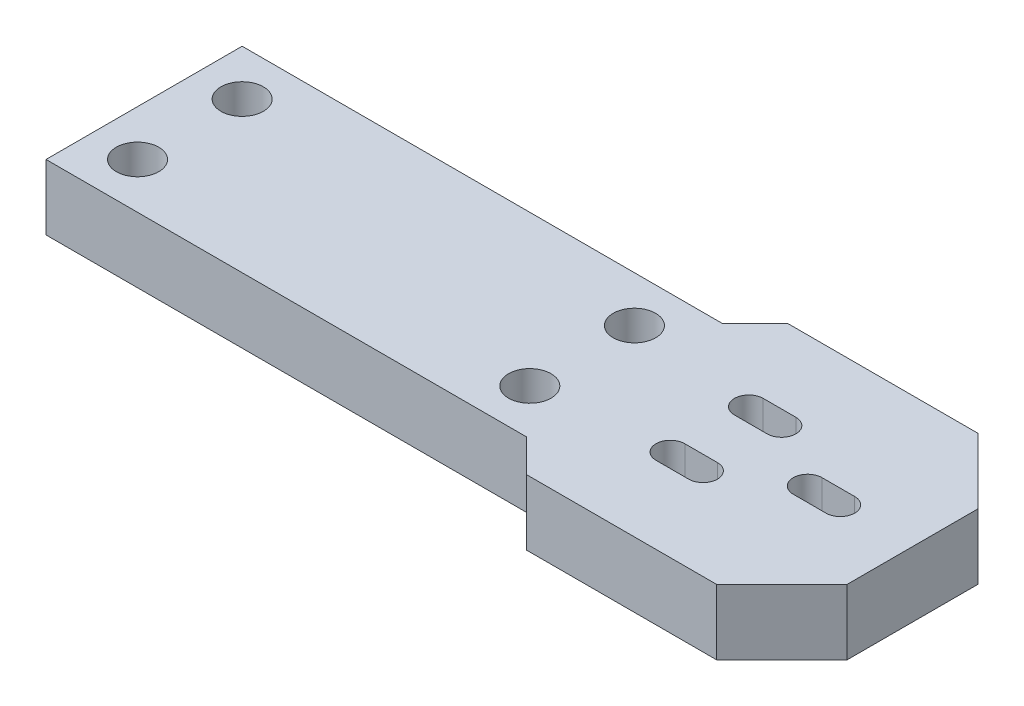
SolidWorks part; units mm, degrees
ref_plane "Front Plane" through (0, 0, 0) normal (0, 0, 1) x (1, 0, 0)
ref_plane "Top Plane" through (0, 0, 0) normal (0, 1, 0) x (1, 0, 0)
ref_plane "Right Plane" through (0, 0, 0) normal (1, 0, 0) x (0, 0, -1)
sketch "Sketch1" plane through (0, 0, 0) normal (0, 1, 0) x (1, 0, 0)
  line L0 (0, 16) -> (0, 0) construction
  line L1 (0, 0) -> (60, 0) construction
  line L2 (0, 16) -> (60, 16) construction
  line L3 (-7, 23) -> (-7, -7)
  line L4 (-7, 23) -> (66.5, 23)
  line L5 (60, 16) -> (66.5, 16) construction
  line L6 (66.5, -7) -> (-7, -7)
  line L7 (110.5518, 8) -> (66.5, 8) construction
  line L8 (110.5518, 28) -> (110.5518, -12)
  line L9 (99.5, 8) -> (94.5, 8) construction
  line L10 (99.5, 5.8) -> (94.5, 5.8)
  line L11 (66.5, 23) -> (66.5, 28)
  line L12 (66.5, 28) -> (110.5518, 28)
  line L13 (99.5, 10.2) -> (94.5, 10.2)
  line L14 (84.5, 14) -> (79.5, 14) construction
  line L15 (110.5518, -12) -> (66.5, -12)
  line L16 (66.5, -12) -> (66.5, -7)
  line L17 (84.5, 11.8) -> (79.5, 11.8)
  line L18 (84.5, 16.2) -> (79.5, 16.2)
  line L19 (84.5, 2) -> (79.5, 2) construction
  line L20 (84.5, -0.2) -> (79.5, -0.2)
  line L21 (84.5, 4.2) -> (79.5, 4.2)
  line L22 (82, 14) -> (82, 8) construction
  line L23 (82, 8) -> (82, 2) construction
  circle A0 centre (0, 0) radius 3.25
  circle A1 centre (0, 16) radius 3.25
  circle A2 centre (60, 0) radius 3.25
  circle A3 centre (60, 16) radius 3.25
  arc A4 (99.5, 5.8) -> (99.5, 10.2) centre (99.5, 8) ccw
  arc A5 (94.5, 10.2) -> (94.5, 5.8) centre (94.5, 8) ccw
  arc A6 (84.5, 11.8) -> (84.5, 16.2) centre (84.5, 14) ccw
  arc A7 (79.5, 16.2) -> (79.5, 11.8) centre (79.5, 14) ccw
  arc A8 (84.5, -0.2) -> (84.5, 4.2) centre (84.5, 2) ccw
  arc A9 (79.5, 4.2) -> (79.5, -0.2) centre (79.5, 2) ccw
  point P11 (-7, 8)
  point P12 (0, 8)
  point P20 (97, 8)
  point P31 (82, 14)
  point P36 (82, 2)
  dimension "D1" = 6.5
  dimension "D11" = 15
  dimension "D12" = 22
  dimension "D7" = 2.2
  dimension "D2" = 16
  dimension "D3" = 60
  dimension "D4" = 30
  dimension "D5" = 7
  dimension "D6" = 6.5
  dimension "D8" = 5
  dimension "D9" = 40
  dimension "D10" = 6
  dimension "D13" = 6.5
extrude "Boss-Extrude1" add sketch "Sketch1" along normal blind 10
chamfer "Chamfer1" distance 10 angle 45 2 edges at (110.5518, 5, 12) (110.5518, 5, -28)
chamfer "Chamfer2" distance 5 angle 45 2 edges at (66.5, 5, 12) (66.5, 5, -28)
